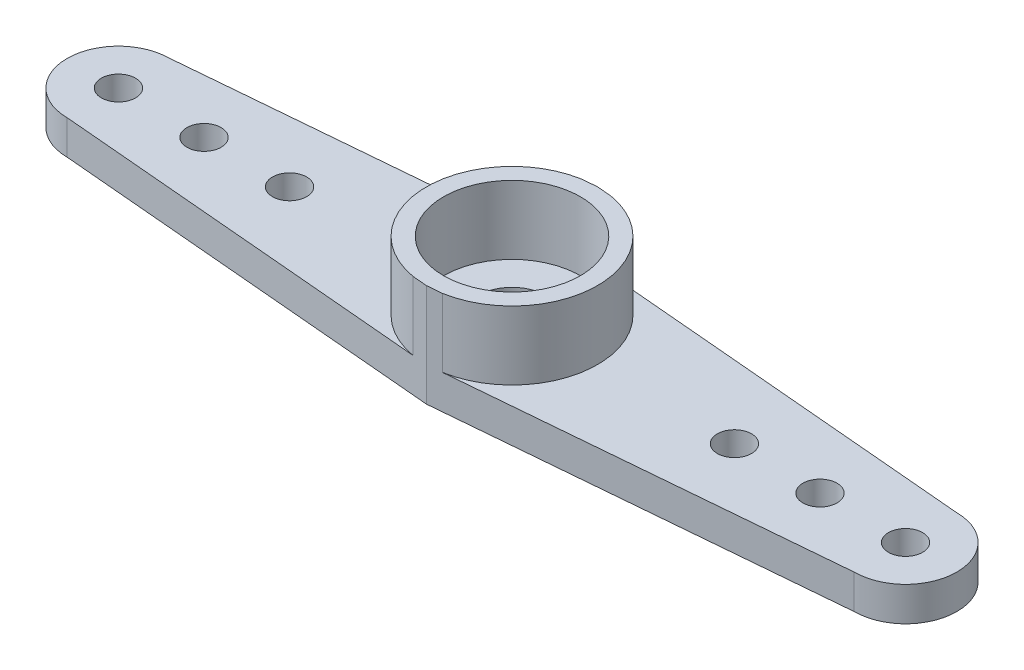
SolidWorks part; units mm, degrees
ref_plane "Front Plane" through (0, 0, 0) normal (0, 0, 1) x (1, 0, 0)
ref_plane "Top Plane" through (0, 0, 0) normal (0, 1, 0) x (1, 0, 0)
ref_plane "Right Plane" through (0, 0, 0) normal (1, 0, 0) x (0, 0, -1)
sketch "Sketch1" plane through (0, 0, 0) normal (0, 1, 0) x (1, 0, 0)
  line L0 (0, 0) -> (11.5, 0) construction
  line L1 (0, 0) -> (6.5, 0) construction
  line L2 (6.5, 0) -> (9, 0) construction
  line L3 (11.5, 1.5) -> (0, 2.5)
  line L4 (0, -2.5) -> (11.5, -1.5)
  line L5 (-11.5, -1.5) -> (0, -2.5)
  line L6 (0, 2.5) -> (-11.5, 1.5)
  line L7 (-11.5, 0) -> (-11.5, 1.5) construction
  circle A0 centre (0, 0) radius 2.5
  circle A1 centre (0, 0) radius 2
  circle A2 centre (0, 0) radius 1
  circle A3 centre (11.5, 0) radius 1.5
  circle A4 centre (11.5, 0) radius 0.5
  circle A5 centre (9, 0) radius 0.5
  circle A6 centre (6.5, 0) radius 0.5
  circle A7 centre (-6.5, 0) radius 0.5
  circle A8 centre (-9, 0) radius 0.5
  circle A9 centre (-11.5, 0) radius 1.5
  circle A10 centre (-11.5, 0) radius 0.5
  point P30 (0, 0)
  dimension "D1" = 2
  dimension "D2" = 11.5
  dimension "D3" = 1.5
extrude "Boss-Extrude1" add sketch "Sketch1" along normal blind 1 contours A9 L5 A0 L6 A7 A8 | L4 A0 L3 L6 L5 A1 | A1 A2 | A3 L3 A0 L4 A6 A5 | A3 A4 | A9 A10 region at (5.8384, 0, 0) region at (12.5307, 0, -1.0307) region at (1.8601, 0, -1.5625) region at (-5.8384, 0, 0) region at (-10.4693, 0, -1.0307) region at (-1.9434, 0, 0)
extrude "Boss-Extrude2" add sketch "Sketch1<4>" along normal blind 3 contours L4 A0 L3 L6 L5 A1 region at (1.8601, 0, -1.5625)
sketch "Sketch1<4>" plane through (0, 0, 0) normal (0, 1, 0) x (1, 0, 0) same geometry as "Sketch1"
